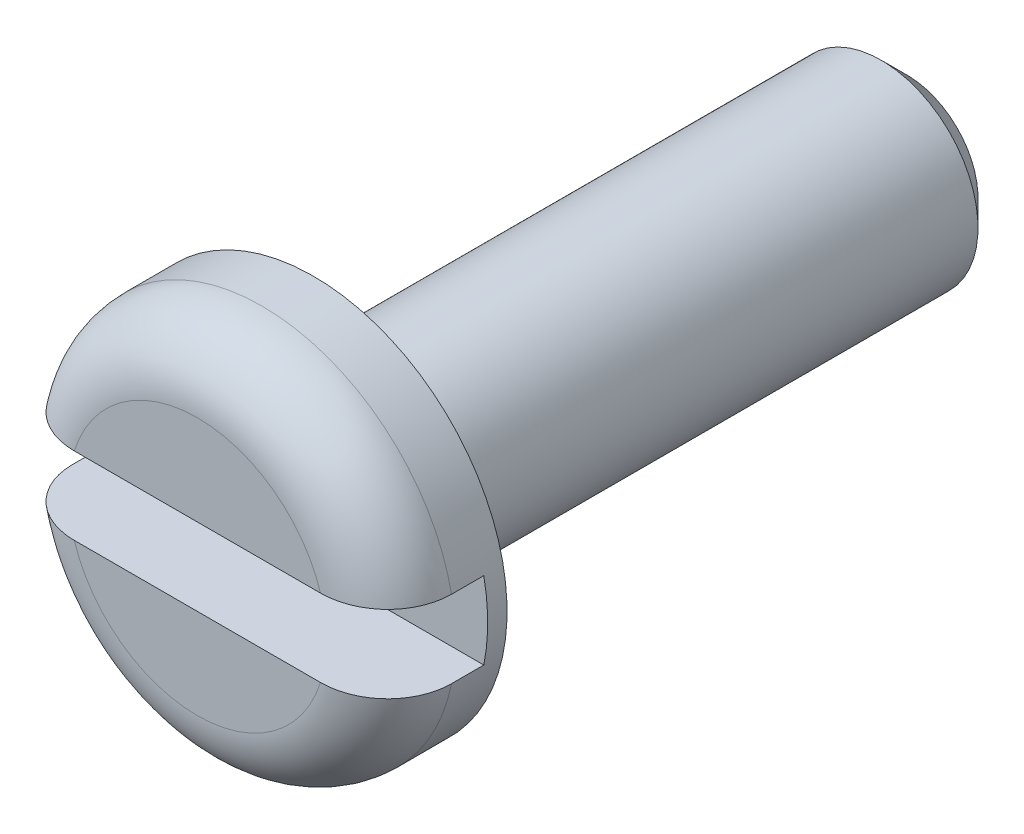
SolidWorks part; units mm, degrees
material "Простая углеродистая сталь"
ref_plane "Спереди" through (0, 0, 0) normal (0, 0, 1) x (1, 0, 0)
ref_plane "Сверху" through (0, 0, 0) normal (0, 1, 0) x (1, 0, 0)
ref_plane "Справа" through (0, 0, 0) normal (1, 0, 0) x (0, 0, -1)
sketch "Эскиз1" plane through (0, 0, 0) normal (0, 1, 0) x (1, 0, 0)
  line L0 (0, 0) -> (-3, 0)
  line L1 (-3, 0) -> (-3, 1.8)
  line L2 (-3, 1.8) -> (-1.5, 1.8)
  line L3 (-1.5, 1.8) -> (-1.5, 11)
  line L4 (-1.5, 11) -> (0, 11)
  line L5 (0, 11) -> (0, 0)
  dimension "D1" = 3
  dimension "D2" = 1.8
  dimension "D3" = 11
  dimension "D4" = 1.5
revolve "Повернуть1" add sketch "Эскиз1" angle 360 about L5
sketch "Эскиз2" plane through (0, 0, 0) normal (1, 0, 0) x (0, 0, -1)
  line L0 (0, 0) -> (22.6818, 0) construction
  line L1 (0, -0.6) -> (0, 0.6)
  line L2 (0, 0.6) -> (1.5, 0.6)
  line L3 (0, -0.6) -> (1.5, -0.6)
  line L4 (1.5, 0.6) -> (1.5, -0.6)
  point P7 (0, 0)
  point P10 (1.5, 0)
  dimension "D1" = 1.2
  dimension "D2" = 1.5
extrude "Вырез-Вытянуть1" cut sketch "Эскиз2" against normal through all both and the other way through all
chamfer "Фаска1" distance 0.4 angle 45 1 edges at (-1.5, 0, -11)
fillet "Скругление1" radius 1 2 edges at (0, -3, 0) (0, 3, 0)
fillet "Скругление2" radius 0.4 1 edges at (-1.5, 0, -1.8)
